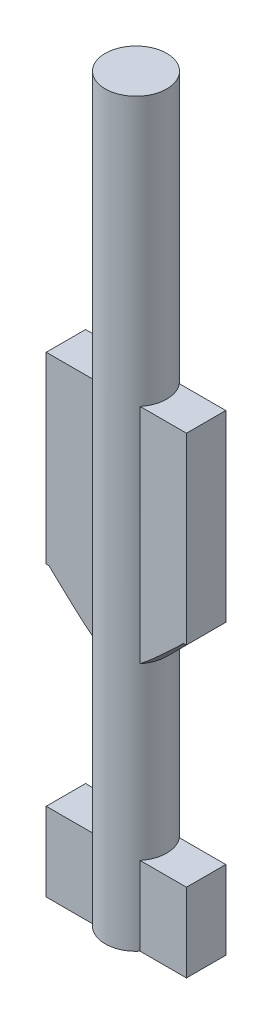
SolidWorks part; units mm, degrees
ref_plane "Front Plane" through (0, 0, 0) normal (0, 0, 1) x (1, 0, 0)
ref_plane "Top Plane" through (0, 0, 0) normal (0, 1, 0) x (1, 0, 0)
ref_plane "Right Plane" through (0, 0, 0) normal (1, 0, 0) x (0, 0, -1)
sketch "Sketch1" plane through (0, 0, 0) normal (0, 1, 0) x (1, 0, 0)
  line L0 (-1.809, -1.5) -> (-5.35, -1.5)
  line L7 (-5.35, -1.5) -> (-5.35, 1.5)
  line L8 (-5.35, 1.5) -> (-1.809, 1.5)
  line L9 (0, 2.35) -> (0, -2.35) construction
  line L10 (5.35, 1.5) -> (1.809, 1.5)
  line L11 (5.35, -1.5) -> (5.35, 1.5)
  line L12 (1.809, -1.5) -> (5.35, -1.5)
  line L13 (-2.35, 0) -> (-5.35, 0) construction
  line L14 (0, 0) -> (-2.35, 0) construction
  circle A0 centre (0, 0) radius 2.35
  point P10 (0, 0)
  dimension "D1" = 4.7
  dimension "D2" = 3
  dimension "D3" = 3
extrude "Boss-Extrude1" add sketch "Sketch1" along normal blind 6 contours A0 L8 L7 L0 | A0 | A0 L12 L11 L10 region at (-3.7605, 0, 0) region at (0, 0, 0) region at (3.7605, 0, 0)
sketch "Sketch2" plane through (0, 6, 0) normal (0, 1, 0) x (1, 0, 0)
  circle A0 centre (0, 0) radius 2.35
  dimension "D1" = 4.7
extrude "Boss-Extrude2" add sketch "Sketch2" along normal blind 16
extrude "Boss-Extrude3" add sketch "Sketch1<2>" along normal blind 14 from surface contours A0 L8 L7 L0 | A0 | A0 L12 L11 L10 region at (-3.7605, 0, 0) region at (0, 0, 0) region at (3.7605, 0, 0) starting at face at (0, 22, 2.35)
sketch "Sketch1<2>" plane through (0, 0, 0) normal (0, 1, 0) x (1, 0, 0) same geometry as "Sketch1"
extrude "Boss-Extrude4" add sketch "Sketch2<2>" along normal blind 20.5 from surface starting at face at (0, 36, 0)
sketch "Sketch2<2>" plane through (0, 6, 0) normal (0, 1, 0) x (1, 0, 0) same geometry as "Sketch2"
chamfer "Chamfer1" distance 3 angle 45 2 edges at (-2.35, 22, 0) (2.35, 22, 0)
